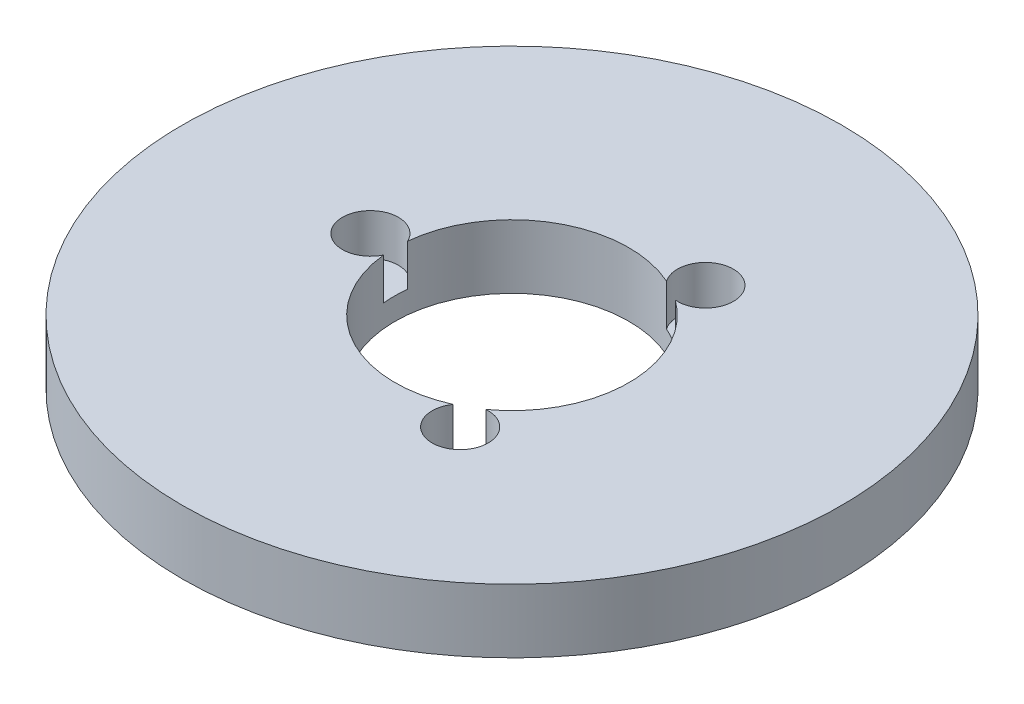
SolidWorks part; units mm, degrees
ref_plane "Front Plane" through (0, 0, 0) normal (0, 0, 1) x (1, 0, 0)
ref_plane "Top Plane" through (0, 0, 0) normal (0, 1, 0) x (1, 0, 0)
ref_plane "Right Plane" through (0, 0, 0) normal (1, 0, 0) x (0, 0, -1)
sketch "Sketch1" plane through (0, 0, 0) normal (0, 1, 0) x (1, 0, 0)
  circle A0 centre (0, 0) radius 77.5
  dimension "FLANGE_OD" = 155
extrude "Boss-Extrude1" add sketch "Sketch1" along normal blind 15
sketch "Sketch2" plane through (0, 0, 0) normal (0, 1, 0) x (1, 0, 0)
  circle A0 centre (0, 0) radius 27.5
  dimension "BORE_D" = 55
extrude "Cut-Extrude1" cut sketch "Sketch2" along normal through all
sketch "Sketch3" plane through (0, 15, 0) normal (0, 1, 0) x (1, 0, 0)
  circle A0 centre (0, 0) radius 33.2963 construction
  circle A1 centre (-33.2963, 0) radius 6.5813
  dimension "BOLT_D" = 13.1627
  dimension "BOLT_PCD" = 66.5925
extrude "Cut-Extrude2" cut sketch "Sketch3" against normal blind 9.7739
pattern_circular "CirPattern1" count 3 over 360 about axis through (0, 0, 0) along (0, 1, 0) of "Cut-Extrude2"
